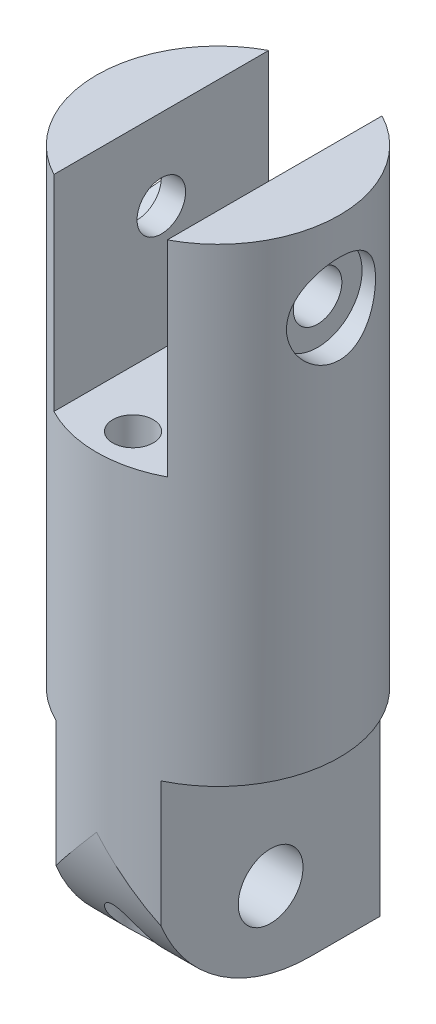
SolidWorks part; units mm, degrees
ref_plane "Front Plane" through (0, 0, 0) normal (0, 0, 1) x (1, 0, 0)
ref_plane "Top Plane" through (0, 0, 0) normal (0, 1, 0) x (1, 0, 0)
ref_plane "Right Plane" through (0, 0, 0) normal (1, 0, 0) x (0, 0, -1)
sketch "Sketch1" plane through (0, 0, 0) normal (0, 0, 1) x (1, 0, 0)
  line L1 (-3.25, 7) -> (3.25, 7)
  line L2 (-3.25, 7) -> (-3.25, -7)
  line L3 (-3.25, -7) -> (3.25, -7)
  line L4 (3.25, 7) -> (3.25, -7)
  line L5 (-3.25, 7) -> (3.25, -7) construction
  line L6 (-3.25, -7) -> (3.25, 7) construction
  point P0 (0, 0)
  dimension "D1" = 6.5
  dimension "D2" = 14
extrude "Boss-Extrude1" add sketch "Sketch1" along normal blind 15
fillet "Fillet1" radius 10 1 edges at (0, -7, 15)
sketch "Sketch2" plane through (3.25, 0, 0) normal (1, 0, 0) x (0, 0, -1)
  line L0 (-7.5, 7) -> (-7.5, -6.6825) construction
  line L1 (-15, 7) -> (0, 7) construction
  arc A0 (-15, 3) -> (-5, -7) centre (-5, 3) ccw construction
  circle A1 centre (-7.5, -2) radius 2
  dimension "D1" = 4
  dimension "D2" = 4.6825
extrude "Cut-Extrude1" cut sketch "Sketch2" against normal through all
sketch "Sketch4" plane through (0, 7, 0) normal (0, 1, 0) x (1, 0, 0)
  line L0 (0, 0) -> (0, -15) construction
  line L1 (3.25, 0) -> (-3.25, 0) construction
  line L2 (3.25, -15) -> (-3.25, -15) construction
  circle A0 centre (0, -7.5) radius 7.5
  dimension "D1" = 15
extrude "Boss-Extrude2" add sketch "Sketch4" along normal blind 29
sketch "Sketch6" plane through (0, 0, 0) normal (0, 0, -1) x (-1, 0, 0)
  line L0 (7.5, 36) -> (-7.5, 36) construction
  line L1 (3.5, 36) -> (-3.5, 36)
  line L2 (3.5, 36) -> (3.5, 23.32)
  line L3 (3.5, 23.32) -> (-3.5, 23.32)
  line L4 (-3.5, 36) -> (-3.5, 23.32)
  point P4 (0, 23.32)
  dimension "D1" = 7
  dimension "D2" = 12.68
extrude "Cut-Extrude2" cut sketch "Sketch6" against normal through all
sketch "Sketch7" plane through (0, 7, 0) normal (0, 1, 0) x (1, 0, 0)
  line L2 (-3.25, -14.2593) -> (-3.25, -15)
  line L3 (-3.25, -15) -> (0, -15)
  line L4 (-3.25, -14.2593) -> (-3.25, -15)
  line L5 (-3.25, -15) -> (0, -15)
  line L6 (0, -15) -> (3.25, -15)
  line L7 (3.25, -15) -> (3.25, -14.2593)
  line L8 (0, -15) -> (3.25, -15)
  line L9 (3.25, -15) -> (3.25, -14.2593)
  line L10 (0, 0) -> (-3.25, 0)
  line L11 (-3.25, 0) -> (-3.25, -0.7407)
  line L12 (0, 0) -> (-3.25, 0)
  line L13 (-3.25, 0) -> (-3.25, -0.7407)
  line L14 (3.25, -0.7407) -> (3.25, 0)
  line L15 (3.25, 0) -> (0, 0)
  line L16 (3.25, -0.7407) -> (3.25, 0)
  line L17 (3.25, 0) -> (0, 0)
  arc A1 (-3.25, -14.2593) -> (0, -15) centre (0, -7.5) ccw
  arc A2 (-3.25, -14.2593) -> (0, -15) centre (0, -7.5) ccw
  arc A3 (0, -15) -> (3.25, -14.2593) centre (0, -7.5) ccw
  arc A4 (0, -15) -> (3.25, -14.2593) centre (0, -7.5) ccw
  arc A5 (0, 0) -> (-3.25, -0.7407) centre (0, -7.5) ccw
  arc A6 (0, 0) -> (-3.25, -0.7407) centre (0, -7.5) ccw
  arc A7 (3.25, -0.7407) -> (0, 0) centre (0, -7.5) ccw
  arc A8 (3.25, -0.7407) -> (0, 0) centre (0, -7.5) ccw
  arc M13 (0, -15) -> (-3.25, -14.2593) centre (0, -7.5) cw
  line M14 (-3.25, -14.2593) -> (-3.25, -15)
  line M15 (-3.25, -15) -> (0, -15)
  dimension "D1" = 0
  dimension "D2" = 0
  dimension "D3" = 0
  dimension "D4" = 0
extrude "Cut-Extrude3" cut sketch "Sketch7" against normal through all contours A6 L12 L13 | A8 L16 L17 | M15 M13 M14 | A4 L8 L9 region at (-2.4457, 7, 14.7798) region at (2.4457, 7, 14.7798) region at (-2.4457, 7, 0.2202) region at (2.4457, 7, 0.2202)
sketch "Sketch8" plane through (-3.5, 0, 0) normal (1, 0, 0) x (0, 0, -1)
  line L0 (-7.5, 23.32) -> (-7.5, 36) construction
  line L1 (-14.1332, 23.32) -> (-0.8668, 23.32) construction
  line L2 (-0.8668, 36) -> (-14.1332, 36) construction
  circle A0 centre (-7.5, 31) radius 1.5
  dimension "D2" = 3
  dimension "D1" = 5
extrude "Cut-Extrude4" cut sketch "Sketch8" against normal mid plane 42
ref_plane "Plane1" through (6.15, 0, 0) normal (-1, 0, 0) x (0, 0, 1)
sketch "Sketch9" plane through (6.15, 0, 0) normal (-1, 0, 0) x (0, 0, 1)
  circle A0 centre (7.5, 31) radius 2.75
  dimension "D1" = 5.5
extrude "Cut-Extrude5" cut sketch "Sketch9" against normal blind 10
ref_plane "Plane2" through (-5, 0, 0) normal (1, 0, 0) x (0, 0, -1)
sketch "Sketch10" plane through (-5, 0, 0) normal (1, 0, 0) x (0, 0, -1)
  line L0 (-7.5, 34.7528) -> (-7.5, 31) construction
  line L1 (-7.5, 34.7528) -> (-10.75, 32.8764)
  line L2 (-10.75, 32.8764) -> (-10.75, 29.1236)
  line L3 (-10.75, 29.1236) -> (-7.5, 27.2472)
  line L4 (-7.5, 27.2472) -> (-4.25, 29.1236)
  line L5 (-4.25, 29.1236) -> (-4.25, 32.8764)
  line L6 (-4.25, 32.8764) -> (-7.5, 34.7528)
  circle A0 centre (-7.5, 31) radius 3.25 construction
  dimension "D1" = 6.5
extrude "Cut-Extrude6" cut sketch "Sketch10" against normal blind 10
sketch "Sketch11" plane through (0, -7, 0) normal (0, -1, 0) x (1, 0, 0)
  line L0 (3.25, 5) -> (-3.25, 5) construction
  circle A1 centre (0, 3) radius 1.25
  circle A3 centre (0, 12.7488) radius 1.25
  dimension "D1" = 2
extrude "Cut-Extrude7" cut sketch "Sketch11" against normal blind 40 contours A3 | A1 region at (0, -7, 3) region at (0, -7, 12.7488)
